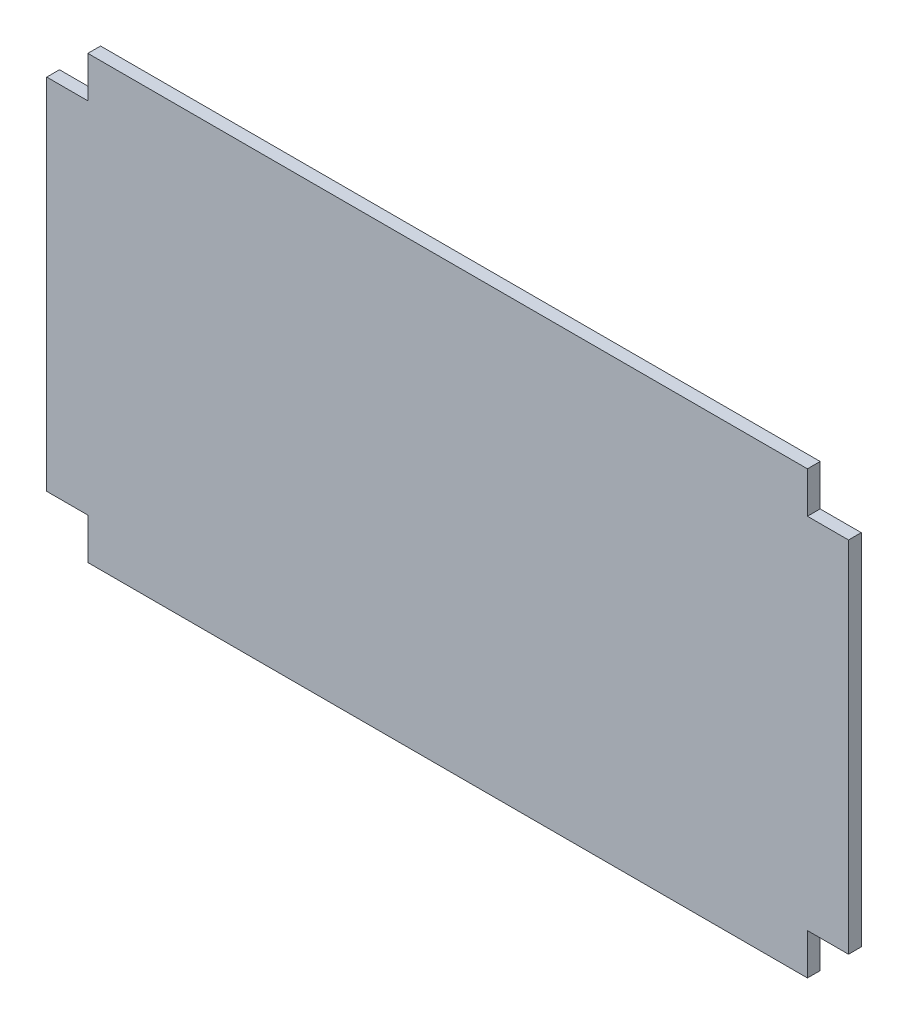
SolidWorks part; units mm, degrees
ref_plane "Front Plane" through (0, 0, 0) normal (0, 0, 1) x (1, 0, 0)
ref_plane "Top Plane" through (0, 0, 0) normal (0, 1, 0) x (1, 0, 0)
ref_plane "Right Plane" through (0, 0, 0) normal (1, 0, 0) x (0, 0, -1)
sketch "Sketch2" plane through (0, 0, 0) normal (0, 0, 1) x (1, 0, 0)
  line L1 (-400, -220) -> (400, -220)
  line L2 (-400, -220) -> (-400, 220)
  line L3 (-400, 220) -> (400, 220)
  line L4 (400, -220) -> (400, 220)
  line L5 (-400, -220) -> (400, 220) construction
  line L6 (-400, 220) -> (400, -220) construction
  point P0 (0, 0)
  dimension "D1" = 800
  dimension "D2" = 440
extrude "Boss-Extrude1" add sketch "Sketch2" along normal blind 12.7
sketch "Sketch3" plane through (0, 0, 12.7) normal (0, 0, 1) x (1, 0, 0)
  line L0 (0, 220) -> (0, -220) construction
  line L1 (-400, 220) -> (-359, 220)
  line L2 (-400, 220) -> (-400, 179)
  line L3 (-400, 179) -> (-359, 179)
  line L4 (-359, 220) -> (-359, 179)
  line L5 (-400, 220) -> (-359, 179) construction
  line L6 (-400, 179) -> (-359, 220) construction
  line L7 (400, 220) -> (-400, 220) construction
  line L8 (-400, -220) -> (400, -220) construction
  line L9 (-400, 0) -> (400, 0) construction
  line L10 (-400, 220) -> (-400, -220) construction
  line L11 (400, -220) -> (400, 220) construction
  line L12 (400, 179) -> (359, 220) construction
  line L13 (400, 220) -> (359, 179) construction
  line L14 (359, 220) -> (359, 179)
  line L15 (400, 179) -> (359, 179)
  line L16 (400, 220) -> (400, 179)
  line L17 (400, 220) -> (359, 220)
  line L18 (400, -220) -> (359, -179) construction
  line L19 (400, -179) -> (359, -220) construction
  line L20 (400, -220) -> (359, -220)
  line L21 (400, -220) -> (400, -179)
  line L22 (359, -220) -> (359, -179)
  line L23 (400, -179) -> (359, -179)
  line L24 (-400, -179) -> (-359, -220) construction
  line L25 (-400, -220) -> (-359, -179) construction
  line L26 (-359, -220) -> (-359, -179)
  line L27 (-400, -179) -> (-359, -179)
  line L28 (-400, -220) -> (-400, -179)
  line L29 (-400, -220) -> (-359, -220)
  point P4 (-379.5, 199.5)
  point P22 (379.5, 199.5)
  point P27 (379.5, -199.5)
  point P32 (-379.5, -199.5)
  dimension "D1" = 41
  dimension "D2" = 41
extrude "Cut-Extrude1" cut sketch "Sketch3" against normal up to next
